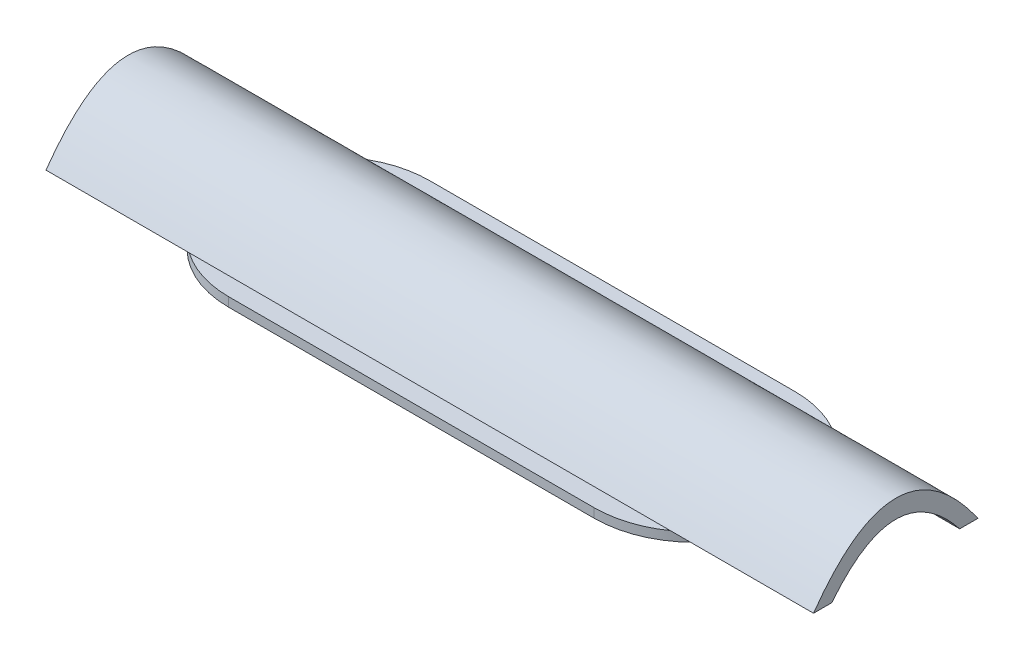
SolidWorks part; units mm, degrees
material "ABS"
ref_plane "Plan de face" through (0, 0, 0) normal (0, 0, 1) x (1, 0, 0)
ref_plane "Plan de dessus" through (0, 0, 0) normal (0, 1, 0) x (1, 0, 0)
ref_plane "Plan de droite" through (0, 0, 0) normal (1, 0, 0) x (0, 0, -1)
sketch "Esquisse1" plane through (0, 0, 0) normal (0, 1, 0) x (1, 0, 0)
  line L0 (-10, 0) -> (10, 0) construction
  line L1 (-10, 3.5) -> (10, 3.5)
  line L2 (-10, -3.5) -> (10, -3.5)
  line L3 (-10, 0) -> (10, 0) construction
  line L4 (-10, 5.5) -> (10, 5.5)
  line L5 (-10, -5.5) -> (10, -5.5)
  arc A0 (-10, 3.5) -> (-10, -3.5) centre (-10, 0) ccw
  arc A1 (10, -3.5) -> (10, 3.5) centre (10, 0) ccw
  arc A2 (-10, 5.5) -> (-10, -5.5) centre (-10, 0) ccw
  arc A3 (10, -5.5) -> (10, 5.5) centre (10, 0) ccw
  point P2 (0, 0)
  point P10 (0, 0)
  dimension "D2" = 7
  dimension "D1" = 20
  dimension "D3" = 2
extrude "Base" add sketch "Esquisse1" along normal blind 0.5
sketch "Esquisse3" plane through (0, 0, 0) normal (1, 0, 0) x (0, 0, -1)
  line L0 (5.5, 0.5) -> (-5.5, 0.5) construction
  line L1 (-4.5, 0.5) -> (-3.5, 0.5)
  line L2 (3.5, 0.5) -> (4.5, 0.5)
  line L3 (-0.0013, 3.7034) -> (-0.0013, 2.7034) construction
  spline S0 degree 2 poles (-3.5, 0.5) (-0.0007, 4.9067) (3.5, 0.5) knots 0 0 0 1 1 1
  spline S1 degree 2 poles (-4.5, 0.5) (0.0105, 6.9067) (4.5, 0.5) knots 0 0 0 1 1 1
  dimension "D1" = 1
extrude "Top" add sketch "Esquisse3" along normal blind 21 and the other way blind 21
sketch "axeZ" plane through (21, 0, 0) normal (1, 0, 0) x (0, 0, -1)
  line L0 (-0.0008, 2.7034) -> (-0.0008, 6.2435) construction
  parabola Q0 (-3.5, 0.5) -> (3.5, 0.5) focus (-0.0006, 1.3134) apex (-0.0008, 2.7034) construction
sketch "Esquisse4" plane through (21, 0, 0) normal (1, 0, 0) x (0, 0, -1)
  line L0 (3.5, 0.5) -> (4.5, 0.5)
  line L1 (-0.0005, 2.7034) -> (0.0097, 3.7034)
  line L2 (-3.5, 0.5) -> (-4.5, 0.5)
  line L3 (3.5, 0.5) -> (4.5, 0.5) construction
  parabola Q0 (4.5, 0.5) -> (-4.5, 0.5) focus (0.0078, 2.123) apex (0.0104, 3.7034) construction
  parabola Q1 (-3.5, 0.5) -> (3.5, 0.5) focus (-0.0006, 1.3134) apex (-0.0008, 2.7034) construction
  spline S0 degree 2 poles (-4.5, 0.5) (0.0066, 6.9067) (4.5, 0.5) knots 0 0 0 1 1 1
  spline S1 degree 2 poles (-3.5, 0.5) (-0.0004, 4.9067) (3.5, 0.5) knots 0 0 0 1 1 1
  point P14 (0, 0)
  point P21 (0, 0)
  point P22 (-3.5, 0.5)
  point P23 (-4.5, 0.5)
  point P25 (4.4558, 0.5)
  point P28 (4.5, 0.5)
revolve "Révolution1" add sketch "Esquisse4" angle 180 about L0 rebuild error yes reverse direction yes
mirror "Symétrie1" about plane through (0, 0, 0) normal (1, 0, 0) rebuild error yes
sketch "Esquisse5" plane through (0, 0, 0) normal (0, -1, 0) x (1, 0, 0)
  line L0 (10, 0) -> (-10, 0) construction
  line L1 (10, -3.5) -> (-10, -3.5)
  line L2 (10, 3.5) -> (-10, 3.5)
  line L3 (-10, 3.5) -> (10, 3.5) construction
  line L4 (-10, 3.5) -> (10, 3.5) construction
  line L5 (-10, 0) -> (10, 0) construction
  line L6 (-10, 2.5) -> (10, 2.5)
  line L7 (-10, -2.5) -> (10, -2.5)
  arc A0 (10, -3.5) -> (10, 3.5) centre (10, 0) ccw
  arc A1 (-10, 3.5) -> (-10, -3.5) centre (-10, 0) ccw
  arc A2 (-10, 2.5) -> (-10, -2.5) centre (-10, 0) ccw
  arc A3 (10, -2.5) -> (10, 2.5) centre (10, 0) ccw
  point P2 (0, 0)
  point P14 (0, 0)
  dimension "D1" = 1
extrude "Boss.-Extru.1" add sketch "Esquisse5" along normal blind 1 and the other way blind 0.5
